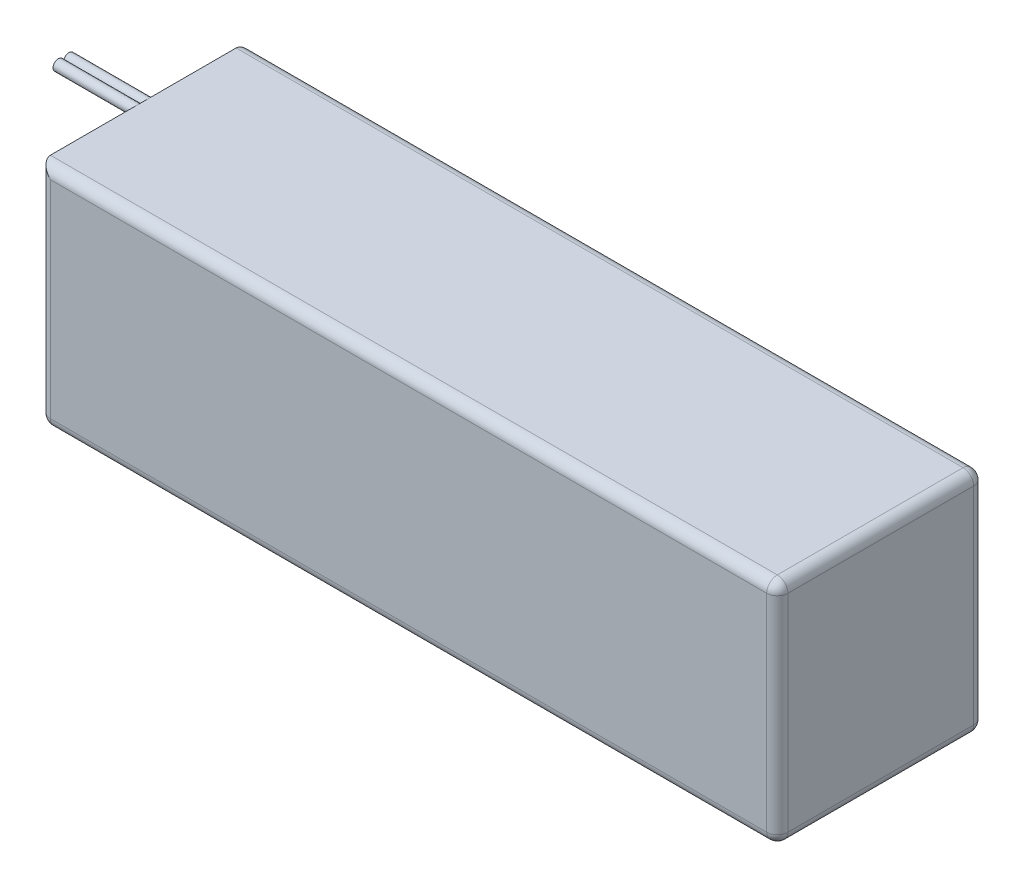
SolidWorks part; units mm, degrees
ref_plane "Front Plane" through (0, 0, 0) normal (0, 0, 1) x (1, 0, 0)
ref_plane "Top Plane" through (0, 0, 0) normal (0, 1, 0) x (1, 0, 0)
ref_plane "Right Plane" through (0, 0, 0) normal (1, 0, 0) x (0, 0, -1)
sketch "Sketch1" plane through (0, 0, 0) normal (0, 0, 1) x (1, 0, 0)
  line L1 (-69.5, -21.5) -> (69.5, -21.5)
  line L2 (-69.5, -21.5) -> (-69.5, 21.5)
  line L3 (-69.5, 21.5) -> (69.5, 21.5)
  line L4 (69.5, -21.5) -> (69.5, 21.5)
  line L5 (-69.5, -21.5) -> (69.5, 21.5) construction
  line L6 (-69.5, 21.5) -> (69.5, -21.5) construction
  point P0 (0, 0)
  dimension "D1" = 139
  dimension "D2" = 43
extrude "Boss-Extrude1" add sketch "Sketch1" along normal blind 39
sketch "Sketch2" plane through (-69.5, 0, 0) normal (-1, 0, 0) x (0, 0, 1)
  line L0 (39, 21.5) -> (0, 21.5) construction
  line L1 (18.495, 20.5) -> (20.505, 20.5) construction
  circle A0 centre (18.495, 20.5) radius 1
  circle A1 centre (20.505, 20.5) radius 1
  point P4 (0, 0)
  point P7 (23.1308, 15.5582)
  point P8 (19.5, 21.5)
  point P9 (19.5, 20.5)
  dimension "D1" = 2
  dimension "D2" = 2.01
extrude "Boss-Extrude4" add sketch "Sketch2" along normal blind 15 separate body
fillet "Fillet1" radius 2 11 edges at (-69.5, 0, 0) (-69.5, -21.5, 19.5) (0, -21.5, 0) (69.5, -21.5, 19.5) (69.5, 0, 0) (0, -21.5, 39) (-69.5, 0, 39) (69.5, 0, 39) (69.5, 21.5, 19.5) (0, 21.5, 39) (0, 21.5, 0)
